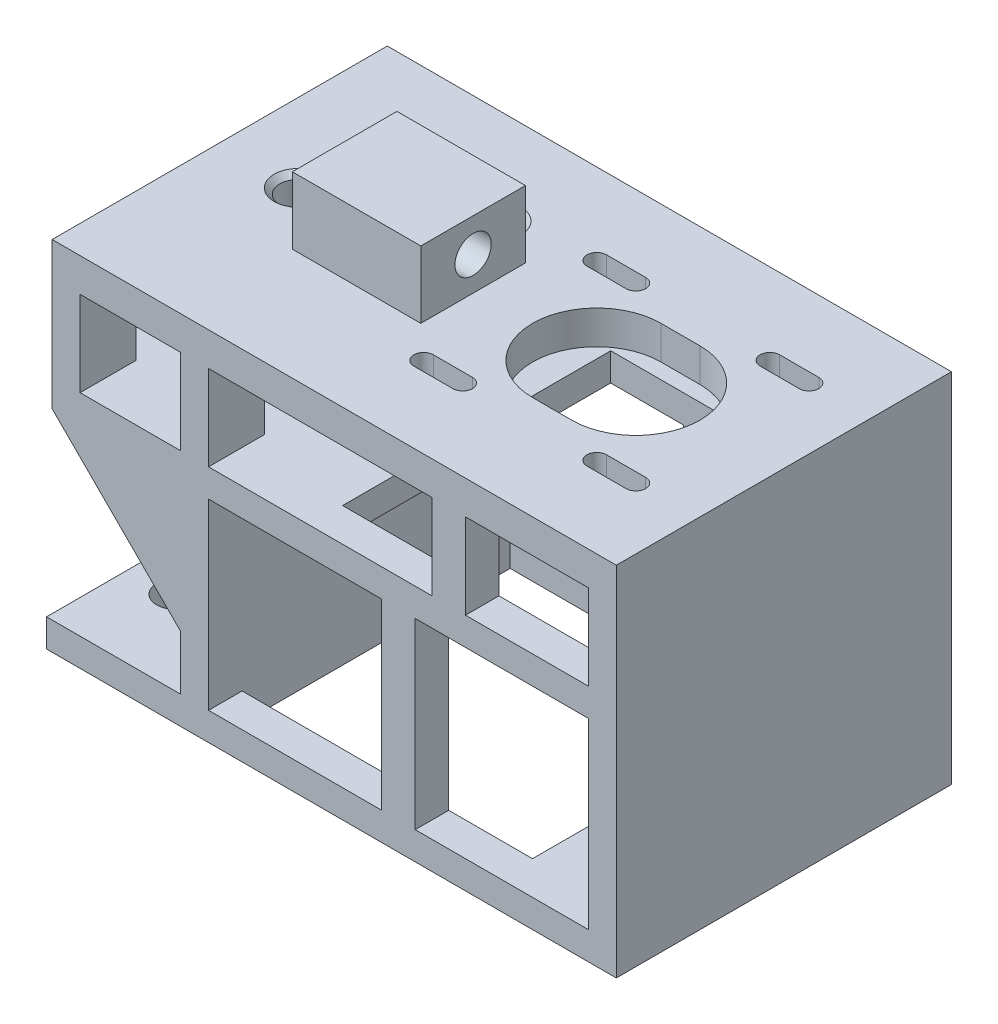
SolidWorks part; units mm, degrees
material "PET"
ref_plane "Front Plane" through (0, 0, 0) normal (0, 0, 1) x (1, 0, 0)
ref_plane "Top Plane" through (0, 0, 0) normal (0, 1, 0) x (1, 0, 0)
ref_plane "Right Plane" through (0, 0, 0) normal (1, 0, 0) x (0, 0, -1)
sketch "Sketch1" plane through (0, 0, 0) normal (0, 0, 1) x (1, 0, 0)
  line L0 (0, 0) -> (-29, 0)
  line L1 (-29, 0) -> (-29, 5)
  line L2 (-29, 5) -> (-5, 5)
  line L3 (-5, 5) -> (-5, 37.75)
  line L4 (-5, 76) -> (18, 76)
  line L5 (18, 76) -> (18, 64)
  line L6 (18, 64) -> (73, 64)
  line L7 (73, 64) -> (73, 0)
  line L10 (73, 0) -> (52, 0)
  line L11 (68, 5) -> (68, 37.75)
  line L12 (68, 58) -> (0, 58)
  line L13 (0, 58) -> (0, 42.75)
  line L14 (0, 42.75) -> (68, 42.75)
  line L16 (68, 37.75) -> (0, 37.75)
  line L17 (0, 0) -> (0, 37.75)
  line L18 (-5, 64) -> (-28, 64)
  line L19 (-28, 64) -> (-28, 37.75)
  line L20 (-28, 37.75) -> (-5, 37.75)
  line L21 (-5, 58) -> (-23, 58)
  line L22 (-23, 58) -> (-23, 42.75)
  line L23 (-23, 42.75) -> (-5, 42.75)
  line L24 (-5, 64) -> (-5, 76)
  line L25 (-5, 42.75) -> (-5, 58)
  line L26 (68, 5) -> (52, 5)
  line L27 (52, 5) -> (52, 0)
  line L28 (68, 42.75) -> (68, 58)
  point P19 (0, 18.875)
  point P28 (-29, 2.5)
  dimension "D1" = 5
  dimension "D2" = 6
  dimension "D3" = 5
  dimension "D4" = 102
  dimension "D5" = 5
  dimension "D6" = 15.25
  dimension "D7" = 42.75
  dimension "D10" = 21
  dimension "D11" = 23
  dimension "D12" = 12
  dimension "D13" = 23
  dimension "D14" = 5
  dimension "D15" = 5
  dimension "D16" = 24
extrude "Boss-Extrude1" add sketch "Sketch1" along normal blind 60
sketch "Sketch2" plane through (0, 0, 0) normal (1, 0, 0) x (0, 0, -1)
  line L0 (-60, 0) -> (-60, 64) construction
  line L1 (-50, 58) -> (-10, 58)
  line L2 (-50, 58) -> (-50, 42.75)
  line L3 (-50, 42.75) -> (-10, 42.75)
  line L4 (-10, 58) -> (-10, 42.75)
  line L5 (-60, 64) -> (0, 64) construction
  line L6 (0, 0) -> (0, 64) construction
  dimension "D1" = 10
  dimension "D2" = 15.25
  dimension "D3" = 6
  dimension "D4" = 10
extrude "Cut-Extrude1" cut sketch "Sketch2" against normal through all
sketch "Sketch3" plane through (0, 64, 0) normal (0, 1, 0) x (1, 0, 0)
  line L0 (18, -30) -> (68, -30) construction
  line L1 (18, -60) -> (18, 0) construction
  line L3 (39.5, -30) -> (46.5, -30) construction
  line L4 (39.5, -18.5) -> (46.5, -18.5)
  line L5 (39.5, -41.5) -> (46.5, -41.5)
  line L6 (31, -14.5) -> (24, -14.5) construction
  line L7 (31, -16.25) -> (24, -16.25)
  line L8 (31, -12.75) -> (24, -12.75)
  line L9 (43, -30) -> (43, 0) construction
  line L12 (73, 0) -> (18, 0) construction
  line L13 (55, -14.5) -> (62, -14.5) construction
  line L14 (55, -16.25) -> (62, -16.25)
  line L15 (55, -12.75) -> (62, -12.75)
  line L16 (31, -45.5) -> (24, -45.5) construction
  line L17 (31, -43.75) -> (24, -43.75)
  line L18 (31, -47.25) -> (24, -47.25)
  line L19 (55, -45.5) -> (62, -45.5) construction
  line L20 (55, -43.75) -> (62, -43.75)
  line L21 (55, -47.25) -> (62, -47.25)
  arc A0 (39.5, -18.5) -> (39.5, -41.5) centre (39.5, -30) ccw
  arc A1 (46.5, -41.5) -> (46.5, -18.5) centre (46.5, -30) ccw
  arc A2 (31, -16.25) -> (31, -12.75) centre (31, -14.5) ccw
  arc A3 (24, -12.75) -> (24, -16.25) centre (24, -14.5) ccw
  arc A4 (55, -16.25) -> (55, -12.75) centre (55, -14.5) cw
  arc A5 (62, -12.75) -> (62, -16.25) centre (62, -14.5) cw
  arc A6 (31, -43.75) -> (31, -47.25) centre (31, -45.5) cw
  arc A7 (24, -47.25) -> (24, -43.75) centre (24, -45.5) cw
  arc A8 (55, -43.75) -> (55, -47.25) centre (55, -45.5) ccw
  arc A9 (62, -47.25) -> (62, -43.75) centre (62, -45.5) ccw
  point P8 (43, -30)
  point P15 (27.5, -14.5)
  point P24 (58.5, -14.5)
  point P31 (27.5, -45.5)
  point P38 (58.5, -45.5)
  dimension "D2" = 11.5
  dimension "D4" = 1.75
  dimension "D1" = 7
  dimension "D3" = 7
  dimension "D5" = 15.5
  dimension "D6" = 15.5
  dimension "D7" = 50
extrude "Cut-Extrude2" cut sketch "Sketch3" against normal up to next
sketch "Sketch5" plane through (0, 76, 0) normal (0, 1, 0) x (1, 0, 0)
  line L0 (18, -30) -> (-5, -30) construction
  line L1 (18, -60) -> (18, 0) construction
  line L2 (-5, -60) -> (-5, 0) construction
  line L3 (18, -60) -> (18, 0) construction
  circle A0 centre (9, -17.27) radius 3.25
  dimension "D1" = 6.5
  dimension "D2" = 12.73
  dimension "D3" = 9
extrude "Cut-Extrude3" cut sketch "Sketch5" against normal up to next
sketch "Sketch6" plane through (0, 42.75, 0) normal (0, 1, 0) x (1, 0, 0)
  circle A0 centre (9, -17.27) radius 2.75
  dimension "D1" = 5.5
extrude "Cut-Extrude4" cut sketch "Sketch6" against normal up to next
sketch "Sketch7" plane through (0, 64, 0) normal (0, 1, 0) x (1, 0, 0)
  line L0 (28, -30) -> (-28, -30) construction
  line L1 (-28, -60) -> (-28, 0) construction
  line L2 (-5, -60) -> (-5, 0) construction
  arc A0 (39.5, -18.5) -> (39.5, -41.5) centre (39.5, -30) ccw construction
  circle A1 centre (-14, -30) radius 2.75
  dimension "D1" = 9
  dimension "D2" = 5.5
extrude "Cut-Extrude5" cut sketch "Sketch7" against normal through all
sketch "Sketch8" plane through (0, 64, 0) normal (0, 1, 0) x (1, 0, 0)
  circle A0 centre (-14, -30) radius 3.25
  dimension "D1" = 6.5
extrude "Cut-Extrude6" cut sketch "Sketch8" against normal up to next
sketch "Sketch9" plane through (0, 76, 0) normal (0, 1, 0) x (1, 0, 0)
  line L0 (18, -60) -> (18, 0) construction
  line L1 (-5, 0) -> (18, 0)
  line L2 (-5, 0) -> (-5, -21.27)
  line L3 (-5, -21.27) -> (18, -21.27)
  line L4 (18, 0) -> (18, -21.27)
  line L6 (-5, -60) -> (18, -60)
  line L7 (-5, -60) -> (-5, -40)
  line L8 (-5, -40) -> (18, -40)
  line L9 (18, -60) -> (18, -40)
  circle A0 centre (9, -17.27) radius 3.25 construction
  dimension "D1" = 4
  dimension "D2" = 20
extrude "Cut-Extrude7" cut sketch "Sketch9" against normal up to surface (12 mm away) up to face at (58.5, 64, 45.5)
chamfer "Chamfer1" distance 1 angle 45 2 edges at (-14, 64, 33.25) (9, 64, 14.02)
ref_plane "Plane1" through (9, 0, 0) normal (1, 0, 0) x (0, 0, -1)
sketch "Sketch10" plane through (0, 0, 0) normal (0, -1, 0) x (1, 0, 0)
  line L0 (-21, 60) -> (-21, 0) construction
  line L1 (-29, 60) -> (0, 60) construction
  line L2 (-29, 0) -> (0, 0) construction
  line L3 (60, 60) -> (60, 0) construction
  line L4 (52, 60) -> (73, 60) construction
  line L5 (52, 0) -> (73, 0) construction
  line L6 (0, 60) -> (0, 0) construction
  line L7 (-21, 45) -> (60, 45) construction
  line L8 (-29, 30) -> (73, 30) construction
  line L9 (-29, 60) -> (-29, 0) construction
  line L11 (-21, 15) -> (60, 15) construction
  line L12 (73, 60) -> (73, 0) construction
  line L13 (52, 60) -> (52, 0) construction
  circle A0 centre (-21, 45) radius 3.3
  circle A1 centre (-21, 15) radius 3.3
  circle A2 centre (60, 15) radius 2.75
  circle A3 centre (60, 45) radius 2.75
  dimension "D5" = 6.6
  dimension "D6" = 6.6
  dimension "D7" = 5.5
  dimension "D8" = 5.5
  dimension "D1" = 21
  dimension "D2" = 15
  dimension "D3" = 15
  dimension "D4" = 8
extrude "Cut-Extrude8" cut sketch "Sketch10" against normal up to next
sketch "Sketch11" plane through (-5, 0, 0) normal (-1, 0, 0) x (0, 0, 1)
  line L0 (21.27, 64) -> (40, 76) construction
  line L1 (60, 64) -> (0, 64) construction
  line L2 (40, 64) -> (21.27, 64) construction
  circle A0 centre (30.635, 70) radius 3.25
  dimension "D1" = 6.5
extrude "Cut-Extrude9" cut sketch "Sketch11" against normal through all
chamfer "Chamfer2" distance 1 angle 45 1 edges at (-5, 66.75, 30.635)
sketch "Sketch12" plane through (0, 42.75, 0) normal (0, 1, 0) x (1, 0, 0)
  line L0 (73, -60) -> (73, 0) construction
  line L1 (18, -6) -> (68, -6)
  line L2 (18, -6) -> (18, -54)
  line L3 (18, -54) -> (68, -54)
  line L4 (68, -6) -> (68, -54)
  line L5 (18, -40) -> (18, -21.27) construction
  line L6 (73, 0) -> (-28, 0) construction
  line L7 (73, -60) -> (-28, -60) construction
  dimension "D1" = 5
  dimension "D2" = 6
  dimension "D3" = 6
extrude "Cut-Extrude10" cut sketch "Sketch12" against normal up to surface (5 mm away) up to face at (9, 37.75, 20.02)
sketch "Sketch13" plane through (0, 0, 0) normal (0, -1, 0) x (1, 0, 0)
  line L0 (52, 60) -> (52, 0) construction
  line L1 (0, 60) -> (52, 60)
  line L2 (0, 60) -> (0, 54)
  line L3 (0, 54) -> (52, 54)
  line L4 (52, 60) -> (52, 54)
  line L5 (68, 54) -> (18, 54) construction
  line L6 (18, 6) -> (68, 6) construction
  line L7 (0, 0) -> (52, 0)
  line L8 (0, 0) -> (0, 6)
  line L9 (0, 6) -> (52, 6)
  line L10 (52, 0) -> (52, 6)
extrude "Boss-Extrude2" add sketch "Sketch13" against normal up to surface (5 mm away) up to face at (62.75, 5, 45)
sketch "Sketch14" plane through (0, 0, 60) normal (0, 0, 1) x (1, 0, 0)
  line L0 (0, 37.75) -> (68, 37.75) construction
  line L1 (31, 37.75) -> (37, 37.75)
  line L2 (31, 37.75) -> (31, 5)
  line L3 (31, 5) -> (37, 5)
  line L4 (37, 37.75) -> (37, 5)
  line L5 (68, 5) -> (0, 5) construction
  line L6 (0, 5) -> (0, 37.75) construction
  dimension "D1" = 6
  dimension "D2" = 31
extrude "Boss-Extrude3" add sketch "Sketch14" against normal up to surface (6 mm away) up to face at (26, 2.5, 54)
sketch "Sketch15" plane through (0, 0, 60) normal (0, 0, 1) x (1, 0, 0)
  line L0 (43, 64) -> (43, 42.75) construction
  line L1 (73, 64) -> (-28, 64) construction
  line L2 (0, 42.75) -> (68, 42.75) construction
  line L3 (39.5, 58) -> (39.5, 64) construction
  line L4 (68, 58) -> (0, 58) construction
  line L5 (40, 58) -> (46, 58)
  line L6 (40, 58) -> (40, 42.75)
  line L7 (40, 42.75) -> (46, 42.75)
  line L8 (46, 58) -> (46, 42.75)
  dimension "D1" = 3.5
  dimension "D2" = 6
  dimension "D3" = 3
extrude "Boss-Extrude4" add sketch "Sketch15" against normal up to surface (6 mm away) up to face at (34.3333, 21.375, 54)
ref_plane "Plane2" through (0, 0, 30) normal (0, 0, 1) x (1, 0, 0)
mirror "Mirror1" about plane through (0, 0, 30) normal (0, 0, 1) of "Boss-Extrude3", "Boss-Extrude4"
sketch "Sketch16" plane through (0, 0, 60) normal (0, 0, 1) x (1, 0, 0)
  line L0 (-28, 37.75) -> (-5, 14.75)
  line L1 (-5, 37.75) -> (-5, 5) construction
  line L2 (-5, 14.75) -> (-5, 37.75)
  line L3 (-5, 37.75) -> (-28, 37.75)
  dimension "D1" = 45
extrude "Boss-Extrude5" add sketch "Sketch16" against normal up to surface (10 mm away) up to face at (-25.5, 50.375, 50)
